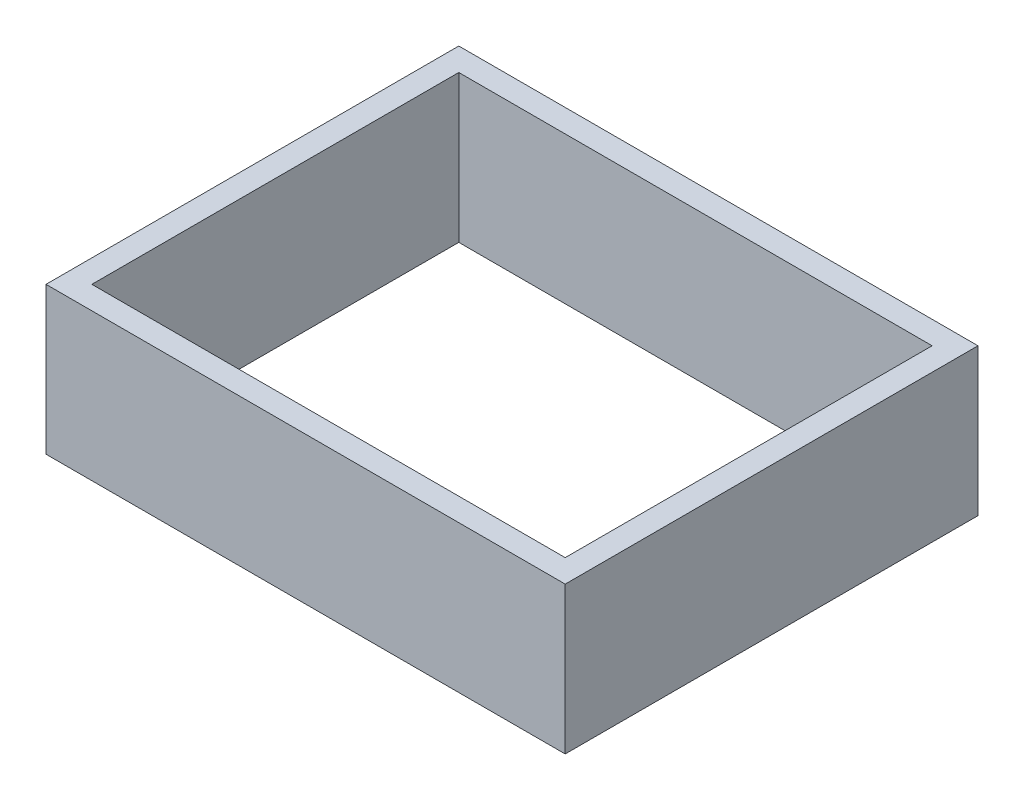
SolidWorks part; units mm, degrees
ref_plane "Front Plane" through (0, 0, 0) normal (0, 0, 1) x (1, 0, 0)
ref_plane "Top Plane" through (0, 0, 0) normal (0, 1, 0) x (1, 0, 0)
ref_plane "Right Plane" through (0, 0, 0) normal (1, 0, 0) x (0, 0, -1)
sketch "Sketch1" plane through (0, 0, 0) normal (0, 1, 0) x (1, 0, 0)
  line L1 (0, 0) -> (283, 0)
  line L2 (0, 0) -> (0, 225)
  line L3 (0, 225) -> (283, 225)
  line L4 (283, 0) -> (283, 225)
  dimension "D1" = 225
  dimension "D2" = 283
extrude "Boss-Extrude1" add sketch "Sketch1" along normal blind 80.2 contours L1 L4 L3 L2
sketch "Sketch2" plane through (0, 80.2, 0) normal (0, 1, 0) x (1, 0, 0)
  line L14 (12.5, 12.5) -> (270.5, 12.5)
  line L15 (270.5, 12.5) -> (270.5, 212.5)
  line L16 (270.5, 212.5) -> (12.5, 212.5)
  line L17 (12.5, 212.5) -> (12.5, 12.5)
  line L18 (12.5, 12.5) -> (270.5, 12.5)
  line L19 (270.5, 12.5) -> (270.5, 212.5)
  line L20 (270.5, 212.5) -> (12.5, 212.5)
  line L21 (12.5, 212.5) -> (12.5, 12.5)
  dimension "D1" = 12.5
extrude "Cut-Extrude1" cut sketch "Sketch2" against normal up to surface (80.2 mm away) contours L21 L18 L19 L20 up to face at (141.5, 0, -112.5)
equation "\"Length\" = 283"
equation "\"Width\" = 225"
equation "\"WallThickness\" = 12.5"
equation "\"UpperWaterJacketThickness\" = 28"
equation "\"D1@Sketch1\"=\"Width\""
equation "\"D2@Sketch1\"=\"Length\""
equation "\"SpacerHeight\" = 80.2"
equation "\"D1@Boss-Extrude1\"=\"SpacerHeight\""
equation "\"D1@Sketch2\"=\"WallThickness\""
